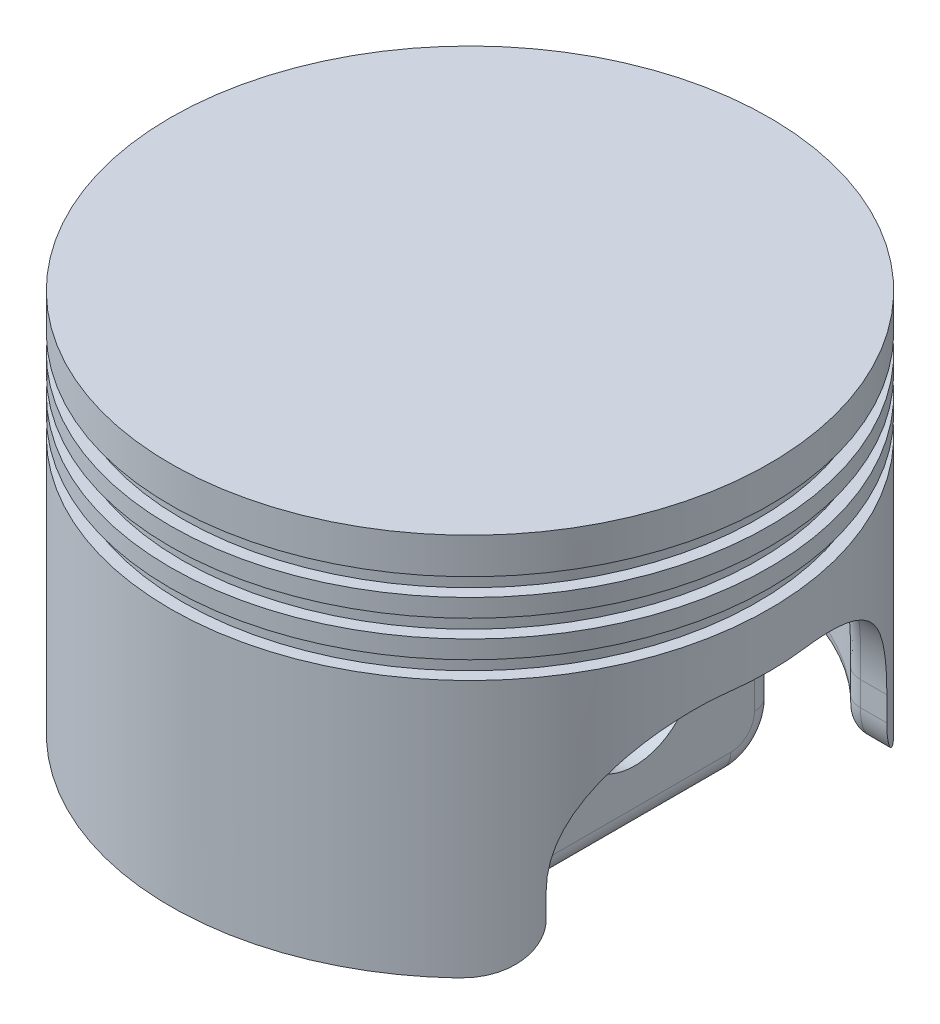
SolidWorks part; units mm, degrees
ref_plane "Front Plane" through (0, 0, 0) normal (0, 0, 1) x (1, 0, 0)
ref_plane "Top Plane" through (0, 0, 0) normal (0, 1, 0) x (1, 0, 0)
ref_plane "Right Plane" through (0, 0, 0) normal (1, 0, 0) x (0, 0, -1)
sketch "Sketch1" plane through (0, 0, 0) normal (0, 0, 1) x (1, 0, 0)
  line L0 (0, 0) -> (0, -19)
  line L1 (0, -19) -> (57.15, -19)
  line L2 (57.15, -19) -> (57.15, -81.28)
  line L3 (57.15, -81.28) -> (63.5, -81.28)
  line L4 (63.5, -81.28) -> (63.5, 0)
  line L5 (63.5, 0) -> (0, 0)
  dimension "D1" = 63.5
  dimension "D2" = 81.28
  dimension "D3" = 19
  dimension "D4" = 57.15
revolve "Revolve1" add sketch "Sketch1" angle 360 about L0
sketch "Sketch2" plane through (0, 0, 0) normal (1, 0, 0) x (0, 0, -1)
  line L0 (-63.5, -81.28) -> (63.5, -81.28) construction
  line L1 (-36.1, -81.28) -> (36.1, -81.28)
  line L2 (-36.1, -81.28) -> (-36.1, -38.1)
  line L3 (-36.1, -38.1) -> (36.1, -38.1)
  line L4 (36.1, -81.28) -> (36.1, -38.1)
  line L5 (-36.1, -81.28) -> (36.1, -38.1) construction
  line L6 (-36.1, -38.1) -> (36.1, -81.28) construction
  point P0 (0, -59.69)
  dimension "D1" = 72.2
  dimension "D2" = 43.18
extrude "Cut-Extrude1" cut sketch "Sketch2" against normal through all both and the other way through all
sketch "Sketch3" plane through (0, 0, 0) normal (1, 0, 0) x (0, 0, -1)
  line L0 (63.5, -81.28) -> (63.5, 0) construction
  line L1 (60.96, -7.62) -> (66.04, -7.62)
  line L2 (60.96, -7.62) -> (60.96, -11.43)
  line L3 (60.96, -11.43) -> (66.04, -11.43)
  line L4 (66.04, -7.62) -> (66.04, -11.43)
  line L5 (60.96, -7.62) -> (66.04, -11.43) construction
  line L6 (60.96, -11.43) -> (66.04, -7.62) construction
  line L7 (63.5, 0) -> (-63.5, 0) construction
  line L8 (0, 0) -> (0, -38.1) construction
  line L9 (-36.1, -38.1) -> (36.1, -38.1) construction
  point P0 (63.5, -9.525)
  dimension "D1" = 3.81
  dimension "D2" = 2.54
  dimension "D3" = 7.62
revolve "Cut-Revolve1" cut sketch "Sketch3" angle 360 about L8
pattern_linear "LPattern1" count 3 spacing 7.62 along (0, -1, 0) of "Cut-Revolve1"
sketch "Sketch4" plane through (0, -19, 0) normal (0, -1, 0) x (1, 0, 0)
  line L0 (0, 0) -> (0, 40.9943) construction
  line L1 (15.88, 30.4) -> (34.88, 30.4)
  line L2 (-15.88, -30.4) -> (-34.88, -30.4)
  line L3 (-15.88, -30.4) -> (-15.88, 30.4)
  line L4 (-15.88, 30.4) -> (-34.88, 30.4)
  line L5 (-34.88, -30.4) -> (-34.88, 30.4)
  line L6 (-15.88, -30.4) -> (-34.88, 30.4) construction
  line L7 (-15.88, 30.4) -> (-34.88, -30.4) construction
  line L8 (34.88, -30.4) -> (34.88, 30.4)
  line L9 (15.88, -30.4) -> (34.88, -30.4)
  line L10 (15.88, -30.4) -> (15.88, 30.4)
  point P3 (-25.38, 0)
  dimension "D1" = 19
  dimension "D2" = 60.8
  dimension "D3" = 31.76
extrude "Boss-Extrude1" add sketch "Sketch4" along normal blind 63.5
sketch "Sketch5" plane through (34.88, 0, 0) normal (1, 0, 0) x (0, 0, -1)
  line L0 (30.4, -82.5) -> (-30.4, -82.5) construction
  circle A0 centre (0, -57.1) radius 12.7
  dimension "D1" = 25.4
  dimension "D2" = 25.4
extrude "Cut-Extrude2" cut sketch "Sketch5" against normal through all both
fillet "Fillet1" radius 28 4 edges at (-48.2725, -38.1, -36.1) (-48.2725, -38.1, 36.1) (48.2725, -38.1, -36.1) (48.2725, -38.1, 36.1)
fillet "Fillet2" radius 10 8 edges at (48.2725, -81.28, -36.1) (-48.2725, -81.28, -36.1) (-48.2725, -81.28, 36.1) (48.2725, -81.28, 36.1) (25.38, -82.5, 30.4) (25.38, -82.5, -30.4) (-25.38, -82.5, 30.4) (-25.38, -82.5, -30.4)
fillet "Fillet3" radius 5 36 edges at (34.88, -45.75, -30.4) (34.88, -79.5711, -27.4711) (34.88, -45.75, 30.4) (34.88, -79.5711, 27.4711) (15.88, -45.75, 30.4) (15.88, -79.5711, 27.4711) (15.88, -45.75, -30.4) (15.88, -79.5711, -27.4711) (-15.88, -45.75, -30.4) (-15.88, -79.5711, -27.4711) (-15.88, -45.75, 30.4) (-15.88, -79.5711, 27.4711) (-34.88, -45.75, 30.4) (-34.88, -79.5711, 27.4711) (-34.88, -45.75, -30.4) (-34.88, -79.5711, -27.4711) (41.8131, -78.2803, -38.9588) (44.3048, -68.69, -36.1) (47.598, -50.9255, -31.6315) (57.15, -38.1, 0) (51.4933, -43.6181, 24.7903) (44.3048, -68.69, 36.1) (43.1127, -76.409, 37.5155) (0, -81.28, 57.15) (-41.8131, -78.2803, 38.9588) (-44.3048, -68.69, 36.1) (-47.598, -50.9255, 31.6315) (-57.15, -38.1, 0) (-51.4933, -43.6181, -24.7903) (-44.3048, -68.69, -36.1) (-43.1127, -76.409, -37.5155) (34.88, -82.5, 0) (15.88, -82.5, 0) (-15.88, -82.5, 0) (-34.88, -82.5, 0) (0, -81.28, -57.15)
fillet "Fillet4" radius 5 17 edges at (17.3445, -19, -28.9355) (25.38, -19, -30.4) (33.4155, -19, -28.9355) (34.88, -19, 0) (33.4155, -19, 28.9355) (25.38, -19, 30.4) (17.3445, -19, 28.9355) (15.88, -19, 0) (-57.15, -19, 0) (-33.4155, -19, -28.9355) (-25.38, -19, -30.4) (-17.3445, -19, -28.9355) (-15.88, -19, 0) (-17.3445, -19, 28.9355) (-25.38, -19, 30.4) (-33.4155, -19, 28.9355) (-34.88, -19, 0)
